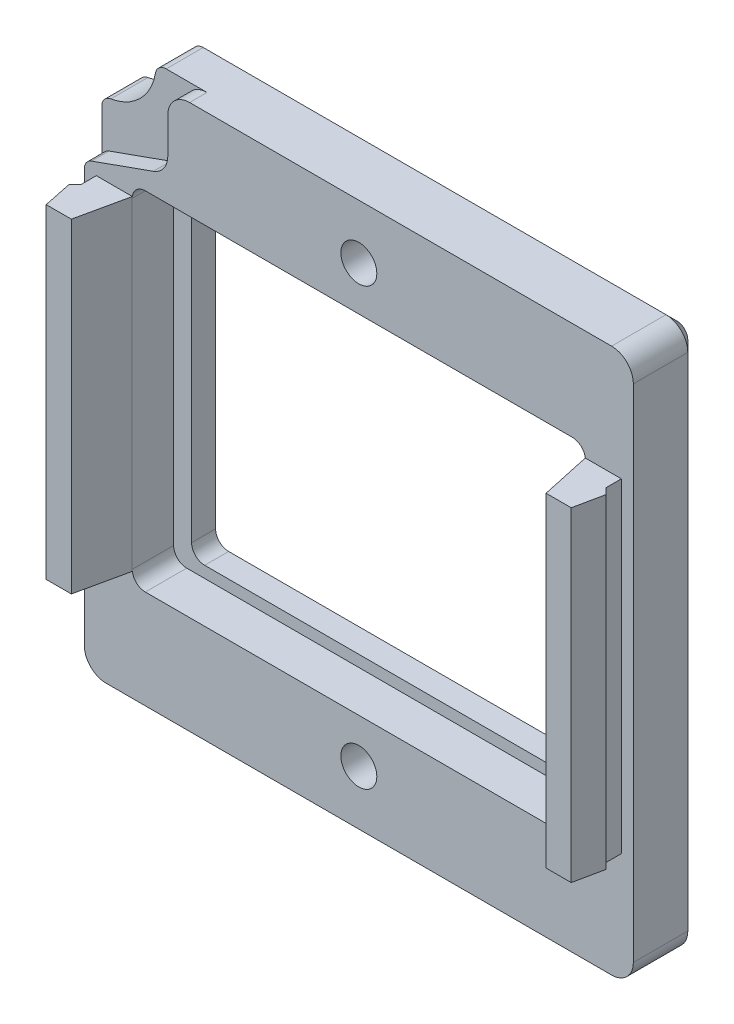
SolidWorks part; units mm, degrees
ref_plane "Front Plane" through (0, 0, 0) normal (0, 0, 1) x (1, 0, 0)
ref_plane "Top Plane" through (0, 0, 0) normal (0, 1, 0) x (1, 0, 0)
ref_plane "Right Plane" through (0, 0, 0) normal (1, 0, 0) x (0, 0, -1)
sketch "Sketch1" plane through (0, 0, 0) normal (0, 0, 1) x (1, 0, 0)
  line L9 (-19.15, -13.7) -> (-19.15, 13.7)
  line L10 (-17.95, -14.9) -> (17.95, -14.9)
  line L11 (19.15, -13.7) -> (19.15, 13.7)
  line L12 (-17.95, 14.9) -> (17.95, 14.9)
  line L26 (25.2, 23) -> (25.2, -23)
  line L27 (23.2, 25) -> (-19.2839, 25)
  line L28 (23.2, -25) -> (-23.2, -25)
  line L30 (-25.2, 19.0839) -> (-25.2, -23)
  arc A6 (19.15, 13.7) -> (17.95, 14.9) centre (17.95, 13.7) ccw
  arc A7 (17.95, -14.9) -> (19.15, -13.7) centre (17.95, -13.7) ccw
  arc A8 (-19.15, -13.7) -> (-17.95, -14.9) centre (-17.95, -13.7) ccw
  arc A9 (-19.15, 13.7) -> (-17.95, 14.9) centre (-17.95, 13.7) cw
  circle A10 centre (0, 20) radius 1.65
  circle A11 centre (0, -20) radius 1.65
  arc A22 (23.2, -25) -> (25.2, -23) centre (23.2, -23) ccw
  arc A23 (25.2, 23) -> (23.2, 25) centre (23.2, 23) ccw
  arc A24 (-23.2, -25) -> (-25.2, -23) centre (-23.2, -23) cw
  arc A28 (-24.3667, 20.0699) -> (-20.2699, 24.1667) centre (-25.2, 25) ccw
  arc A29 (-25.2, 19.0839) -> (-24.3667, 20.0699) centre (-24.2, 19.0839) cw
  arc A30 (-19.2839, 25) -> (-20.2699, 24.1667) centre (-19.2839, 24) ccw
extrude "Boss-Extrude1" add sketch "Sketch1" along normal blind 10.6
sketch "Sketch2" plane through (0, 0, 10.6) normal (0, 0, 1) x (1, 0, 0)
  line L11 (-25.2, 14.9) -> (25.2, 14.9)
  line L12 (-25.2, 14.9) -> (-25.2, -14.9)
  line L13 (-25.2, -14.9) -> (25.2, -14.9)
  line L14 (25.2, 14.9) -> (25.2, -14.9)
extrude "Cut-Extrude1" cut sketch "Sketch2" against normal blind 4.6 flip side to cut
sketch "Sketch3" plane through (0, 0, 10.6) normal (0, 0, 1) x (1, 0, 0)
  line L10 (-20.8, -14.75) -> (-20.8, 14.75)
  line L11 (-19.6, -15.95) -> (19.6, -15.95)
  line L12 (20.8, -14.75) -> (20.8, 14.75)
  line L13 (-19.6, 15.95) -> (19.6, 15.95)
  arc A3 (19.6, -15.95) -> (20.8, -14.75) centre (19.6, -14.75) ccw
  arc A4 (-20.8, -14.75) -> (-19.6, -15.95) centre (-19.6, -14.75) ccw
  arc A5 (20.8, 14.75) -> (19.6, 15.95) centre (19.6, 14.75) ccw
  arc A6 (-20.8, 14.75) -> (-19.6, 15.95) centre (-19.6, 14.75) cw
extrude "Cut-Extrude2" cut sketch "Sketch3" against normal offset from surface (8.4 mm away) 2.2 up to face at (1.65, 20, 0)
sketch "Sketch4" plane through (0, -25, 0) normal (0, -1, 0) x (1, 0, 0)
  line L9 (-24.1, 7.4) -> (-24.65, 7.95)
  line L11 (-24.1, 10.6) -> (-21.7906, 10.6)
  line L14 (24.1, 6) -> (25.2, 6)
  line L15 (-25.2, 0) -> (25.2, 0)
  line L16 (-25.2, 0) -> (-25.2, 6)
  line L17 (-25.2, 6) -> (-24.1, 6)
  line L18 (25.2, 0) -> (25.2, 6)
  line L20 (24.1, 6) -> (24.1, 7.4)
  line L22 (-24.1, 6) -> (-24.1, 7.4)
  line L23 (-24.65, 7.95) -> (-24.1, 10.6)
  line L24 (24.1, 7.4) -> (24.65, 7.95)
  line L25 (24.65, 7.95) -> (24.1, 10.6)
  line L27 (-21.7906, 10.6) -> (-20.7906, 6)
  line L30 (21.7906, 10.6) -> (20.7906, 6)
  line L31 (-20.7906, 6) -> (20.7906, 6)
  line L32 (21.7906, 10.6) -> (24.1, 10.6)
extrude "Cut-Extrude3" cut sketch "Sketch4" against normal up to surface (50 mm away) flip side to cut up to face at (1.958, 25, 3)
sketch "Sketch5" plane through (0, 0, 6) normal (0, 0, 1) x (1, 0, 0)
  line L0 (-17.5363, 19.7512) -> (-17.5363, 23)
  line L1 (-24.5363, 15.8417) -> (-18.8637, 17.8677)
  line L2 (-25.2, 14.9) -> (-25.2, 19.0839)
  line L3 (-19.2839, 25) -> (-15.5363, 25)
  arc A0 (-18.8637, 17.8677) -> (-17.5363, 19.7512) centre (-19.5363, 19.7512) ccw
  arc A1 (-17.5363, 23) -> (-15.5363, 25) centre (-15.5363, 23) cw
  arc A2 (-25.2, 14.9) -> (-24.5363, 15.8417) centre (-24.2, 14.9) cw
  arc A4 (-24.3667, 20.0699) -> (-20.2699, 24.1667) centre (-25.2, 25) ccw
  arc A5 (-25.2, 19.0839) -> (-24.3667, 20.0699) centre (-24.2, 19.0839) cw
  arc A6 (-19.2839, 25) -> (-20.2699, 24.1667) centre (-19.2839, 24) ccw
extrude "Cut-Extrude4" cut sketch "Sketch5" against normal blind 1.6
chamfer "Chamfer1" distance 1 angle 45 10 edges at (0, -25, 0) (24.6142, -24.4142, 0) (-24.6142, -24.4142, 0) (25.2, 0, 0) (24.6142, 24.4142, 0) (-25.2, -1.958, 0) (-24.9638, 19.7294, 0) (-21.6645, 21.4645, 0) (-19.9294, 24.7638, 0) (1.958, 25, 0)
